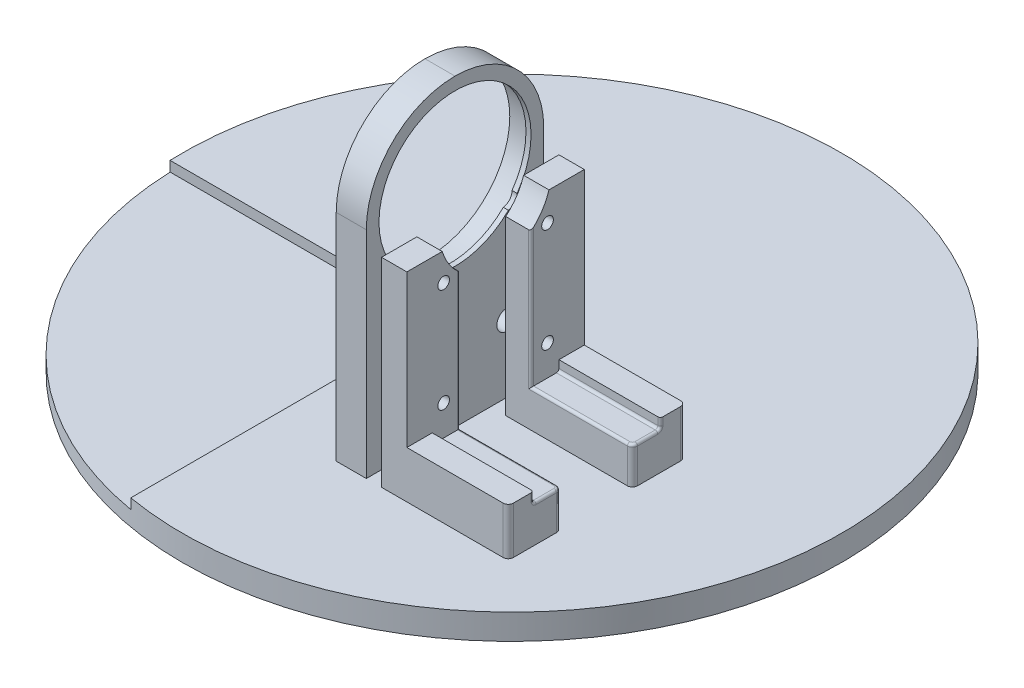
SolidWorks part; units mm, degrees
ref_plane "정면" through (0, 0, 0) normal (0, 0, 1) x (1, 0, 0)
ref_plane "윗면" through (0, 0, 0) normal (0, 1, 0) x (1, 0, 0)
ref_plane "우측면" through (0, 0, 0) normal (1, 0, 0) x (0, 0, -1)
sketch "스케치1" plane through (0, 0, 0) normal (0, 1, 0) x (1, 0, 0)
  circle A0 centre (0, 0) radius 65
  dimension "D1" = 130
extrude "보스-돌출1" add sketch "스케치1" along normal blind 5
sketch "스케치2" plane through (0, 5, 0) normal (0, 1, 0) x (1, 0, 0)
  line L1 (2.76, -2.5) -> (8.76, -2.5)
  line L2 (2.76, -2.5) -> (2.76, -37.5)
  line L3 (2.76, -37.5) -> (8.76, -37.5)
  line L4 (8.76, -2.5) -> (8.76, -37.5)
  point P4 (8.76, -20)
  dimension "D1" = 2.76
  dimension "D2" = 6
  dimension "D3" = 35
  dimension "D4" = 20
extrude "보스-돌출2" add sketch "스케치2" along normal blind 60
fillet "필렛1" radius 17.5 2 edges at (5.76, 65, 2.5) (5.76, 65, 37.5)
sketch "스케치3" plane through (2.76, 0, 0) normal (-1, 0, 0) x (0, 0, 1)
  circle A0 centre (20, 47.5) radius 16
  dimension "D1" = 32
extrude "컷-돌출1" cut sketch "스케치3" against normal blind 5
chamfer "모따기1" distance 0.8 angle 64 1 edges at (2.76, 47.5, 36) first distance on face at (7.76, 47.5, 36)
sketch "스케치4" plane through (7.76, 0, 0) normal (-1, 0, 0) x (0, 0, 1)
  circle A0 centre (20, 47.5) radius 15
  circle A1 centre (20, 47.5) radius 16 construction
  dimension "D1" = 1
extrude "컷-돌출2" cut sketch "스케치4" against normal through all
sketch "스케치6" plane through (8.76, 0, 0) normal (1, 0, 0) x (0, 0, -1)
  line L5 (-2.5, 27.5) -> (-2.5, 21.5)
  line L6 (-2.5, 27.5) -> (-4.5, 27.5)
  line L7 (-2.5, 21.5) -> (-4.5, 21.5)
  line L8 (-4.5, 27.5) -> (-4.5, 21.5)
  line L9 (-2.5, 47.5) -> (-2.5, 5) construction
  circle A0 centre (-20, 47.5) radius 15 construction
  dimension "D4" = 20
  dimension "D2" = 2
extrude "컷-돌출3" cut sketch "스케치6" against normal through all
sketch "스케치8" plane through (0, 0, 4.5) normal (0, 0, -1) x (-1, 0, 0)
  line L0 (-2.76, 27.5) -> (-8.76, 27.5) construction
  line L1 (-2.76, 27.5) -> (-2.76, 21.5) construction
  circle A0 centre (-5.76, 24.5) radius 1.6
  dimension "D1" = 3
  dimension "D2" = 3
  dimension "D3" = 3.2
extrude "컷-돌출5" cut sketch "스케치8" against normal blind 6
sketch "스케치9" plane through (0, 0, 4.5) normal (0, 0, -1) x (-1, 0, 0)
  line L0 (-2.76, 21.5) -> (-8.76, 21.5) construction
  line L3 (-4.3166, 27) -> (-7.2034, 27)
  line L4 (-7.2034, 27) -> (-8.6468, 24.5)
  line L5 (-8.6468, 24.5) -> (-7.2034, 22)
  line L6 (-7.2034, 22) -> (-4.3166, 22)
  line L7 (-4.3166, 27) -> (-2.76, 27)
  line L8 (-2.76, 27.5) -> (-2.76, 21.5) construction
  line L9 (-2.76, 27) -> (-2.76, 22)
  line L10 (-2.76, 22) -> (-4.3166, 22)
  line L12 (-2.8732, 24.5) -> (-4.3166, 27) [skipped]
  line L13 (-4.3166, 22) -> (-2.8732, 24.5) [skipped]
  circle A0 centre (-5.76, 24.5) radius 2.5 construction
  dimension "D1" = 5
extrude "컷-돌출8" cut sketch "스케치9" against normal blind 2.2 from offset 2 offset against normal yes
sketch "스케치11" plane through (0, 5, 0) normal (0, 1, 0) x (1, 0, 0)
  line L0 (11.76, -2.5) -> (36.76, -2.5)
  line L1 (11.76, -2.5) -> (11.76, -13)
  line L2 (36.76, -2.5) -> (36.76, -13)
  line L3 (11.76, -13) -> (36.76, -13)
  line L4 (11.76, -27) -> (36.76, -27)
  line L5 (11.76, -27) -> (11.76, -37.5)
  line L6 (36.76, -27) -> (36.76, -37.5)
  line L7 (11.76, -37.5) -> (36.76, -37.5)
  line L8 (8.76, -2.5) -> (2.76, -2.5) construction
  line L9 (8.76, -37.5) -> (8.76, -2.5) construction
  dimension "D1" = 35
  dimension "D2" = 10.5
  dimension "D3" = 3
  dimension "D4" = 25
extrude "보스-돌출4" add sketch "스케치11" along normal blind 7.3
sketch "스케치12" plane through (0, 12.3, 0) normal (0, 1, 0) x (1, 0, 0)
  line L0 (16.76, -32.5) -> (36.76, -32.5)
  line L1 (11.76, -2.5) -> (36.76, -2.5)
  line L2 (11.76, -2.5) -> (11.76, -13)
  line L3 (11.76, -13) -> (16.76, -13)
  line L4 (36.76, -2.5) -> (36.76, -7.5)
  line L5 (11.76, -27) -> (16.76, -27)
  line L6 (11.76, -27) -> (11.76, -37.5)
  line L7 (11.76, -37.5) -> (36.76, -37.5)
  line L8 (36.76, -32.5) -> (36.76, -37.5)
  line L9 (16.76, -7.5) -> (36.76, -7.5)
  line L10 (16.76, -7.5) -> (16.76, -13)
  line L11 (16.76, -27) -> (16.76, -32.5)
  line L12 (11.76, -13) -> (36.76, -13) construction
  line L13 (11.76, -27) -> (36.76, -27) construction
  line L14 (16.76, -2.5) -> (16.76, -13) construction
  line L15 (11.76, -7.5) -> (36.76, -7.5) construction
  line L16 (11.76, -32.5) -> (36.76, -32.5) construction
  line L17 (16.76, -27) -> (16.76, -37.5) construction
  dimension "D1" = 5.5
  dimension "D2" = 5.5
  dimension "D3" = 5
extrude "보스-돌출5" add sketch "스케치12" along normal blind 2
fillet "필렛3" radius 1 4 edges at (36.76, 8.65, 27) (36.76, 8.65, 13) (36.76, 9.65, 2.5) (36.76, 9.65, 37.5)
sketch "스케치13" plane through (16.76, 0, 0) normal (1, 0, 0) x (0, 0, -1)
  line L0 (-27, 14.3) -> (-37.5, 14.3)
  line L1 (-27, 14.3) -> (-27, 39.0147)
  line L2 (-37.5, 14.3) -> (-37.5, 44.3)
  line L3 (-30.5243, 44.3) -> (-37.5, 44.3)
  line L4 (-13, 14.3) -> (-2.5, 14.3)
  line L5 (-13, 14.3) -> (-13, 39.0147)
  line L6 (-2.5, 14.3) -> (-2.5, 44.3)
  line L7 (-9.4757, 44.3) -> (-2.5, 44.3)
  line L10 (-2.5, 21.5) -> (-2.5, 5) construction
  arc A0 (-30.5243, 44.3) -> (-27, 39.0147) centre (-20, 47.5) ccw
  arc A1 (-13, 39.0147) -> (-9.4757, 44.3) centre (-20, 47.5) ccw
  dimension "D2" = 22
  dimension "D1" = 30
extrude "보스-돌출6" add sketch "스케치13" against normal blind 5
sketch "스케치14" plane through (16.76, 0, 0) normal (1, 0, 0) x (0, 0, -1)
  line L1 (-30.25, 38.8) -> (-9.75, 38.8) construction
  line L2 (-30.25, 38.8) -> (-30.25, 18.3) construction
  line L3 (-30.25, 18.3) -> (-9.75, 18.3) construction
  line L4 (-9.75, 38.8) -> (-9.75, 18.3) construction
  line L8 (-32.5, 12.3) -> (-27, 12.3) construction
  circle A1 centre (-20, 47.5) radius 15 construction
  circle A2 centre (-30.25, 18.3) radius 1.15
  circle A3 centre (-9.75, 18.3) radius 1.15
  circle A4 centre (-9.75, 38.8) radius 1.15
  circle A5 centre (-30.25, 38.8) radius 1.15
  dimension "D5" = 2.3
  dimension "D1" = 20.5
  dimension "D2" = 20.5
  dimension "D3" = 6
  dimension "D4" = 10.25
extrude "컷-돌출10" cut sketch "스케치14" against normal through all
fillet "필렛2" radius 0.5 12 edges at (26.76, 12.3, 32.5) (26.76, 12.3, 7.5) (36.76, 13.3, 7.5) (36.76, 13.3, 32.5) (36.76, 12.3, 9.75) (36.76, 12.3, 30.25) (26.26, 12.3, 13) (36.4671, 12.3, 12.7071) (26.26, 12.3, 27) (36.4671, 12.3, 27.2929) (16.76, 25.6574, 13) (16.76, 25.6574, 27)
sketch "스케치15" plane through (2.76, 0, 0) normal (-1, 0, 0) x (0, 0, 1)
  circle A0 centre (9.75, 38.8) radius 2
  circle A1 centre (30.25, 38.8) radius 2
  circle A2 centre (9.75, 18.3) radius 2
  circle A3 centre (30.25, 18.3) radius 2
  dimension "D1" = 4
extrude "컷-돌출11" cut sketch "스케치15" against normal blind 10
sketch "스케치16" plane through (0, 5, 0) normal (0, 1, 0) x (1, 0, 0)
  line L0 (2.8284, -2.5) -> (2.8284, -20) construction
  line L1 (-11.1716, -2.5) -> (-65, -2.5)
  line L2 (-11.1716, -2.5) -> (-11.1716, -65)
  line L3 (-11.1716, -65) -> (-65, -65)
  line L4 (-65, -2.5) -> (-65, -65)
  line L6 (35.76, -2.5) -> (16.76, -2.5) construction
  circle A0 centre (0, 0) radius 65 construction
  dimension "D2" = 14
extrude "컷-돌출12" cut sketch "스케치16" against normal blind 2
